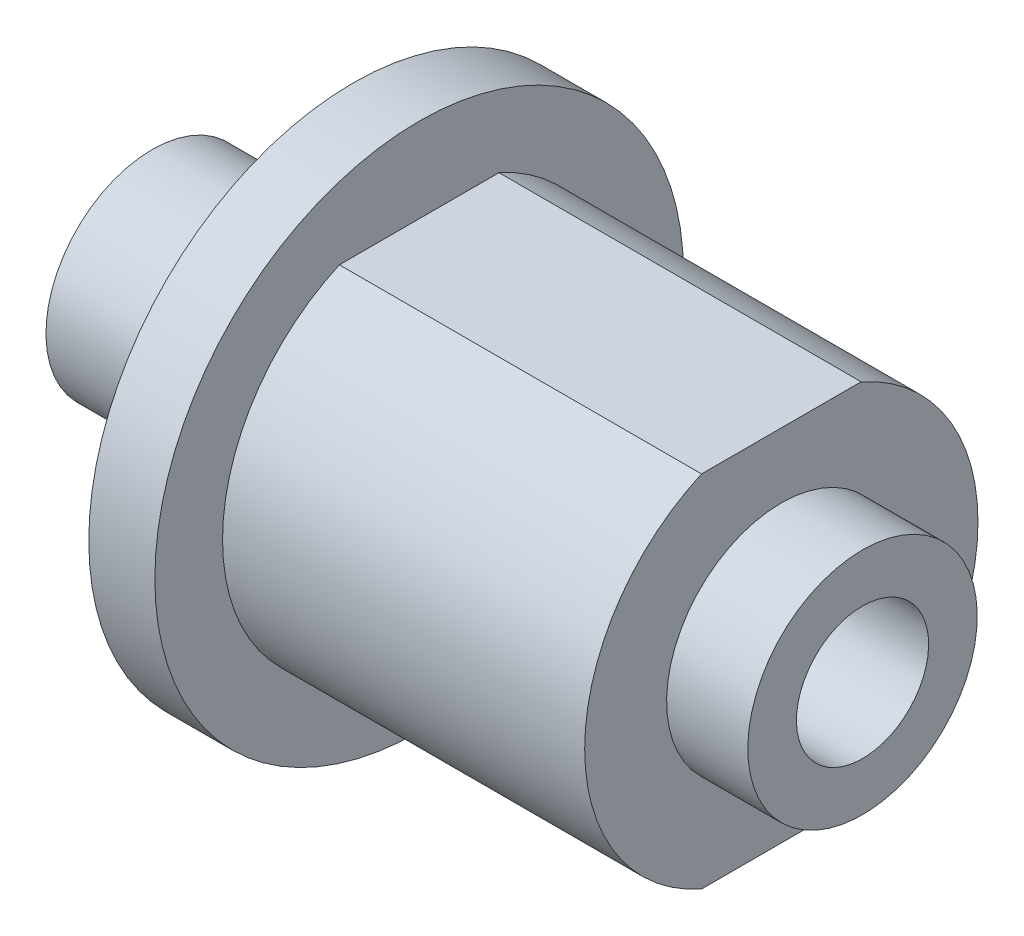
SolidWorks part; units mm, degrees
ref_plane "Front Plane" through (0, 0, 0) normal (0, 0, 1) x (1, 0, 0)
ref_plane "Top Plane" through (0, 0, 0) normal (0, 1, 0) x (1, 0, 0)
ref_plane "Right Plane" through (0, 0, 0) normal (1, 0, 0) x (0, 0, -1)
sketch "Sketch1" plane through (0, 0, 0) normal (0, 0, 1) x (1, 0, 0)
  line L0 (0, 0) -> (0, 5.1054)
  line L1 (0, 5.1054) -> (9.652, 5.1054)
  line L7 (12.827, 9.4488) -> (30.226, 9.4488)
  line L8 (30.226, 9.4488) -> (30.226, 5.5118)
  line L9 (30.226, 5.5118) -> (34.1274, 5.5118)
  line L10 (34.1274, 5.5118) -> (34.1274, 0)
  line L11 (34.1274, 0) -> (0, 0)
  line L12 (34.1274, 3.175) -> (0, 3.175)
  line L13 (34.1274, 0) -> (34.1274, 3.175)
  line L15 (9.652, 5.1054) -> (9.652, 12.7)
  line L16 (9.652, 12.7) -> (12.827, 12.7)
  line L17 (12.827, 12.7) -> (12.827, 9.4488)
  point P7 (0, 0)
  dimension "D1" = 9.652
  dimension "D2" = 17.399
  dimension "D3" = 12.7
  dimension "D5" = 3.9014
  dimension "D6" = 3.937
  dimension "D9" = 5.1054
  dimension "D11" = 3.175
  dimension "D12" = 5.5118
revolve "Revolve1" add sketch "Sketch1" angle 360 about L11
sketch "Sketch2" plane through (0, 0, 0) normal (0, 0, 1) x (1, 0, 0)
  line L2 (12.827, -8.636) -> (30.226, -8.636)
  line L5 (12.827, 9.4488) -> (12.827, 8.636)
  line L6 (12.827, 8.636) -> (30.226, 8.636)
  line L7 (30.226, 8.636) -> (30.226, 9.4488)
  line L8 (30.226, 9.4488) -> (12.827, 9.4488)
  line L9 (12.827, -9.4488) -> (12.827, 9.4488) construction
  line L10 (30.226, -9.4488) -> (30.226, 9.4488) construction
  line L11 (30.226, -8.636) -> (30.226, -9.4488)
  line L12 (30.226, -9.4488) -> (12.827, -9.4488)
  line L13 (12.827, -9.4488) -> (12.827, -8.636)
  point P14 (30.226, 9.4488)
  dimension "D1" = 0.8128
  dimension "D2" = 17.399
  dimension "D3" = 17.272
extrude "Cut-Extrude1" cut sketch "Sketch2" against normal through all both and the other way through all
